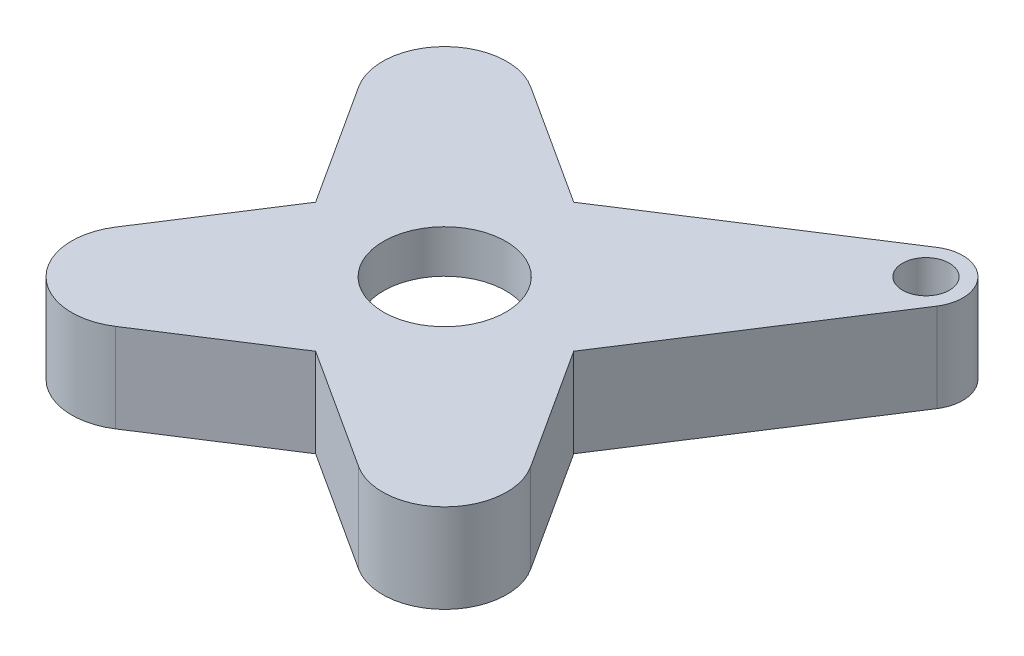
SolidWorks part; units mm, degrees
ref_plane "Front Plane" through (0, 0, 0) normal (0, 0, 1) x (1, 0, 0)
ref_plane "Top Plane" through (0, 0, 0) normal (0, 1, 0) x (1, 0, 0)
ref_plane "Right Plane" through (0, 0, 0) normal (1, 0, 0) x (0, 0, -1)
sketch "Sketch1" plane through (0, 0, 0) normal (0, 1, 0) x (1, 0, 0)
  line L0 (-13.0815, -13.0815) -> (13.0815, 13.0815) construction
  line L1 (-13.0815, 13.0815) -> (13.0815, -13.0815) construction
  line L2 (7.57, 1.4889) -> (13.3608, 10.4574)
  line L3 (1.4889, 7.57) -> (10.4574, 13.3608)
  line L4 (7.57, 1.4889) -> (1.4889, 7.57) construction
  line L5 (13.3608, -10.4574) -> (7.57, -1.4889)
  line L6 (10.4574, -13.3608) -> (1.4889, -7.57)
  line L7 (-13.3608, -10.4574) -> (-7.57, -1.4889)
  line L8 (-10.4574, -13.3608) -> (-1.4889, -7.57)
  line L9 (-10.4574, 13.3608) -> (-1.4889, 7.57)
  line L10 (-7.57, 1.4889) -> (-13.3608, 10.4574)
  line L11 (8.0238, 1.0211) -> (13.8942, 10.113)
  line L12 (1.0211, 8.0238) -> (10.113, 13.8942)
  line L13 (-10.113, 13.8942) -> (-1.0211, 8.0238)
  line L14 (-8.0238, 1.0211) -> (-13.8942, 10.113)
  line L15 (-13.8942, -10.113) -> (-8.0238, -1.0211)
  line L16 (-10.113, -13.8942) -> (-1.0211, -8.0238)
  line L17 (10.113, -13.8942) -> (1.0211, -8.0238)
  line L18 (13.8942, -10.113) -> (8.0238, -1.0211)
  line L19 (9.6321, 0) -> (15.4946, 9.0797)
  line L20 (0, 9.6321) -> (9.0797, 15.4946)
  line L21 (-9.0797, 15.4946) -> (0, 9.6321)
  line L22 (-9.6321, 0) -> (-15.4946, 9.0797)
  line L23 (-15.4946, -9.0797) -> (-9.6321, 0)
  line L24 (-9.0797, -15.4946) -> (0, -9.6321)
  line L25 (9.0797, -15.4946) -> (0, -9.6321)
  line L26 (15.4946, -9.0797) -> (9.6321, 0)
  line L27 (15.4946, 9.0797) -> (20.2671, 16.4712)
  line L28 (9.0797, 15.4946) -> (16.4712, 20.2671)
  circle A0 centre (0, 0) radius 6.7736 construction
  arc A1 (10.4574, 13.3608) -> (13.3608, 10.4574) centre (11.5966, 11.5966) cw
  arc A2 (-1.4889, 7.57) -> (1.4889, 7.57) centre (0, 8.5636) ccw
  arc A3 (7.57, 1.4889) -> (7.57, -1.4889) centre (8.5636, 0) ccw
  arc A4 (-1.4889, -7.57) -> (1.4889, -7.57) centre (0, -8.5636) cw
  arc A5 (13.3608, -10.4574) -> (10.4574, -13.3608) centre (11.5966, -11.5966) cw
  arc A6 (-7.57, 1.4889) -> (-7.57, -1.4889) centre (-8.5636, 0) cw
  arc A7 (-13.3608, -10.4574) -> (-10.4574, -13.3608) centre (-11.5966, -11.5966) ccw
  arc A8 (-13.3608, 10.4574) -> (-10.4574, 13.3608) centre (-11.5966, 11.5966) cw
  arc A11 (10.113, 13.8942) -> (13.8942, 10.113) centre (11.5966, 11.5966) cw
  arc A12 (-1.0211, 8.0238) -> (1.0211, 8.0238) centre (0, 8.5636) ccw
  arc A13 (-13.8942, 10.113) -> (-10.113, 13.8942) centre (-11.5966, 11.5966) cw
  arc A14 (-8.0238, 1.0211) -> (-8.0238, -1.0211) centre (-8.5636, 0) cw
  arc A15 (-13.8942, -10.113) -> (-10.113, -13.8942) centre (-11.5966, -11.5966) ccw
  arc A16 (-1.0211, -8.0238) -> (1.0211, -8.0238) centre (0, -8.5636) cw
  arc A17 (13.8942, -10.113) -> (10.113, -13.8942) centre (11.5966, -11.5966) cw
  arc A18 (8.0238, 1.0211) -> (8.0238, -1.0211) centre (8.5636, 0) ccw
  arc A20 (0, 9.6321) -> (0, 9.6321) centre (0, 9.6321) ccw
  arc A21 (-15.4946, 9.0797) -> (-9.0797, 15.4946) centre (-11.5966, 11.5966) cw
  arc A22 (-9.6321, 0) -> (-9.6321, 0) centre (-9.6321, 0) cw
  arc A23 (-15.4946, -9.0797) -> (-9.0797, -15.4946) centre (-11.5966, -11.5966) ccw
  arc A24 (0, -9.6321) -> (0, -9.6321) centre (0, -9.6321) cw
  arc A25 (15.4946, -9.0797) -> (9.0797, -15.4946) centre (11.5966, -11.5966) cw
  arc A26 (9.6321, 0) -> (9.6321, 0) centre (9.6321, 0) ccw
  arc A27 (9.0797, 15.4946) -> (15.4946, 9.0797) centre (11.5966, 11.5966) cw construction
  arc A28 (16.4712, 20.2671) -> (20.2671, 16.4712) centre (17.9605, 17.9605) cw
  circle A29 centre (17.9605, 17.9605) radius 1.75
  circle A30 centre (0, 0) radius 4.572
  point P5 (0, 0)
  point P8 (0, 0)
  point P31 (4.5294, 4.5294)
  point P66 (0, 0)
  dimension "D2" = 2.1
  dimension "D3" = 1.79
  dimension "D6" = 0.635
  dimension "D8" = 25.4
  dimension "4.5mm" = 3.5
  dimension "D9" = 9.144
  dimension "D1" = 18.5
  dimension "D4" = 7.57
  dimension "D5" = 8.6
  dimension "D7" = 2.54
extrude "Boss-Extrude1" add sketch "Sketch1" along normal blind 3.2004 contours A28 L28 L20 L21 A21 L22 L23 A23 L24 L25 A25 L26 L19 L27 A29 L11 A18 L18 A17 L17 A16 L16 A15 L15 A14 L14 A13 L13 A12 L12 A11 | A8 L10 A6 L7 A7 L8 A4 L6 A5 L5 A3 L2 A1 L3 A2 L9 | A18 L11 A11 L12 A12 L13 A13 L14 A14 L15 A15 L16 A16 L17 A17 L18 L10 A8 L9 A2 L3 A1 L2 A3 L5 A5 L6 A4 L8 A7 L7 A6 region at (6.3862, 0, 0) region at (7.0033, 0, 0) region at (12.1245, 0, 4.8232)
extrude "Boss-Extrude2" add sketch "Sketch1<3>" against normal blind 3.429 contours A28 L28 L20 L21 A21 L22 L23 A23 L24 L25 A25 L26 L19 L27 A29 L11 A18 L18 A17 L17 A16 L16 A15 L15 A14 L14 A13 L13 A12 L12 A11 region at (12.1245, 0, 4.8232)
sketch "Sketch1<3>" plane through (0, 0, 0) normal (0, 1, 0) x (1, 0, 0) same geometry as "Sketch1"
